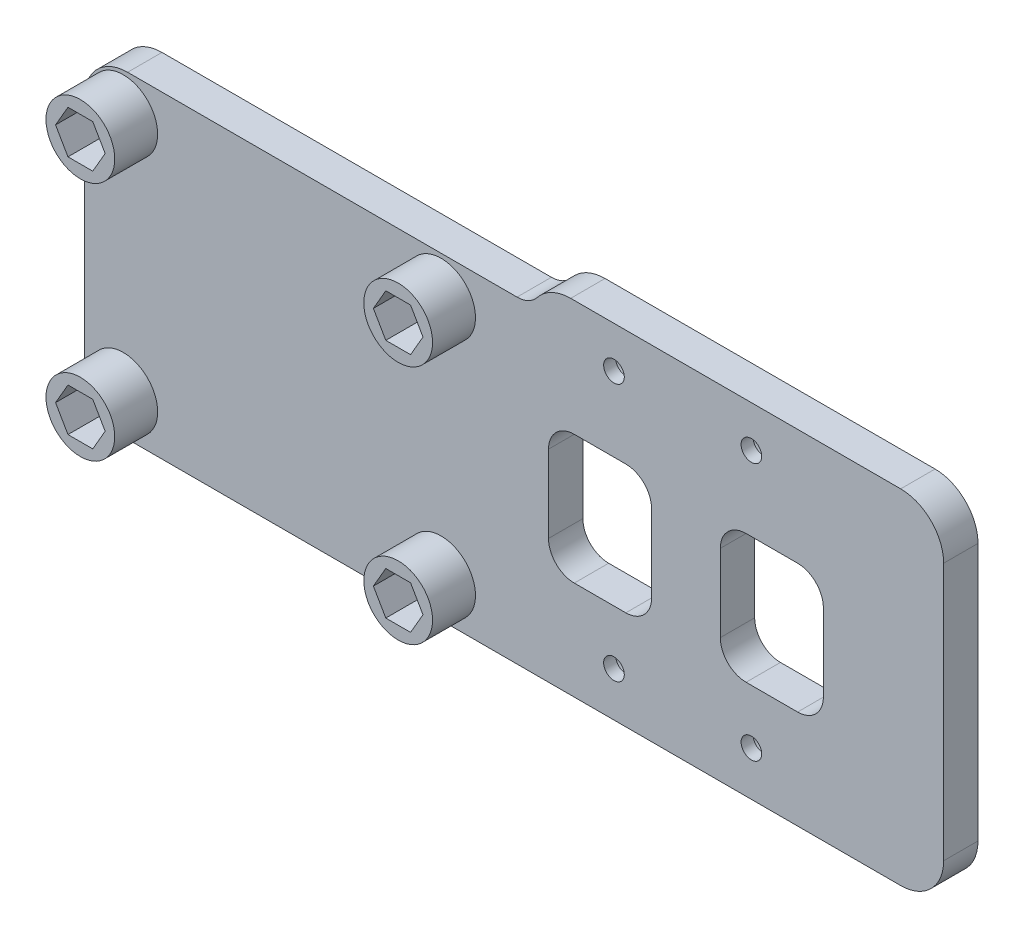
SolidWorks part; units mm, degrees
ref_plane "Front Plane" through (0, 0, 0) normal (0, 0, 1) x (1, 0, 0)
ref_plane "Top Plane" through (0, 0, 0) normal (0, 1, 0) x (1, 0, 0)
ref_plane "Right Plane" through (0, 0, 0) normal (1, 0, 0) x (0, 0, -1)
ref_plane "Plane1" through (0, 0, 34.8116) normal (0, 0, -1) x (-1, 0, 0)
sketch "Sketch1" plane through (0, 0, 34.8116) normal (0, 0, -1) x (-1, 0, 0)
  line L0 (-23.5355, 118.8347) -> (-23.5355, 78.8347)
  line L1 (-23.5355, 78.8347) -> (26.4645, 78.8347)
  line L2 (26.4645, 78.8347) -> (26.4645, 118.8347)
  line L3 (26.4645, 118.8347) -> (-23.5355, 118.8347)
extrude "Boss-Extrude1" add sketch "Sketch1" against normal blind 4
sketch "Sketch2" plane through (0, 0, 38.8116) normal (0, 0, 1) x (1, 0, 0)
  line L0 (23.5355, 90.3347) -> (23.5355, 105.3347)
  line L1 (23.5355, 105.3347) -> (15.5355, 105.3347)
  line L2 (15.5355, 105.3347) -> (15.5355, 90.3347)
  line L3 (15.5355, 90.3347) -> (23.5355, 90.3347)
  line L4 (23.5355, 118.8347) -> (23.5355, 78.8347) construction
  line L6 (15.5355, 105.3347) -> (23.5355, 90.3347) construction
  line L7 (15.5355, 90.3347) -> (23.5355, 105.3347) construction
  line L8 (23.5355, 78.8347) -> (-26.4645, 78.8347) construction
  point P6 (19.5355, 97.8347)
  dimension "D1" = 8
  dimension "D2" = 15
  dimension "D3" = 19
extrude "Cut-Extrude1" cut sketch "Sketch2" against normal through all
sketch "Sketch3" plane through (0, 0, 38.8116) normal (0, 0, 1) x (1, 0, 0)
  line L0 (7.5355, 105.3347) -> (-4.4645, 105.3347)
  line L1 (-4.4645, 105.3347) -> (-4.4645, 90.3347)
  line L2 (-4.4645, 90.3347) -> (7.5355, 90.3347)
  line L3 (7.5355, 90.3347) -> (7.5355, 105.3347)
  line L4 (23.5355, 105.3347) -> (15.5355, 105.3347) construction
  line L5 (15.5355, 90.3347) -> (23.5355, 90.3347) construction
  line L6 (15.5355, 105.3347) -> (15.5355, 90.3347) construction
  dimension "D1" = 8
  dimension "D2" = 12
extrude "Cut-Extrude2" cut sketch "Sketch3" against normal through all
hole_wizard "CBORE for M2 Pan Head Machine Screw1" positions "Sketch5" profile "Sketch4" counterbore size "M2" standard "ANSI Metric" end condition up to next
sketch "Sketch5" plane through (0, 0, 34.8116) normal (0, 0, -1) x (-1, 0, 0)
  point P0 (-3.1566, 84.0163)
  point P1 (-19.1566, 84.0163)
  point P2 (-19.1566, 114.0163)
  point P3 (-3.1566, 114.0163)
sketch "Sketch4" plane through (3.1566, 84.0163, 34.8116) normal (1, 0, 0) x (0, 1, 0)
  line L0 (0, 0) -> (0, 4)
  line L1 (0, 4) -> (1.2, 4)
  line L3 (1.2, 4) -> (1.2, 2.6)
  line L4 (1.2, 2.6) -> (2.5, 2.6)
  line L5 (2.5, 2.6) -> (2.5, 0)
  line L7 (2.5, 0) -> (0, 0)
  line L11 (0, -6.35) -> (0, 107.95) construction
  dimension "Thru Hole Dia." = 2.4
  dimension "Thru Hole Depth" = 4
  dimension "C'Bore Dia." = 5
  dimension "C'Bore Depth" = 2.6
sketch "Sketch6" plane through (0, 0, 38.8116) normal (0, 0, 1) x (1, 0, 0)
  line L0 (-26.4645, 78.8347) -> (-26.4645, 118.8347) construction
  line L1 (-11.4645, 78.8347) -> (-58.4645, 78.8347)
  line L2 (-11.4645, 78.8347) -> (-11.4645, 115.8347)
  line L3 (-11.4645, 115.8347) -> (-58.4645, 115.8347)
  line L4 (-58.4645, 78.8347) -> (-58.4645, 115.8347)
  line L7 (23.5355, 78.8347) -> (-26.4645, 78.8347) construction
  dimension "D1" = 47
  dimension "D2" = 37
  dimension "D3" = 15
extrude "Boss-Extrude2" add sketch "Sketch6" against normal up to surface (4 mm away) up to face at (0.6566, 84.0163, 34.8116)
sketch "Sketch7" plane through (0, 0, 38.8116) normal (0, 0, 1) x (1, 0, 0)
  line L0 (-53.9645, 111.3347) -> (-53.9645, 83.3347) construction
  line L1 (-58.4645, 97.3347) -> (-53.9645, 97.3347) construction
  line L2 (-58.4645, 115.8347) -> (-58.4645, 78.8347) construction
  line L4 (-11.4645, 78.8347) -> (-11.4645, 115.8347) construction
  circle A0 centre (-53.9645, 111.3347) radius 4
  circle A1 centre (-16.9645, 111.3347) radius 4
  circle A2 centre (-53.9645, 83.3347) radius 4
  circle A3 centre (-16.9645, 83.3347) radius 4
  dimension "D3" = 8
  dimension "D1" = 37
  dimension "D2" = 28
  dimension "D4" = 5.5
extrude "Boss-Extrude3" add sketch "Sketch7" along normal blind 5
hole_wizard "Ø2.7 (2.7) Diameter Hole1" positions "Sketch8" profile "Sketch9" hole size "Ø2.7" standard "ANSI Metric"
sketch "Sketch8" plane through (0, 0, 43.8116) normal (0, 0, 1) x (1, 0, 0)
  point P0 (-53.9645, 111.3347)
  point P3 (-16.9645, 111.3347)
  point P6 (-16.9645, 83.3347)
  point P9 (-53.9645, 83.3347)
sketch "Sketch9" plane through (-53.9645, 111.3347, 43.8116) normal (1, 0, 0) x (0, -1, 0)
  line L0 (0, 0) -> (0, 4.8112)
  line L1 (0, 4.8112) -> (1.35, 4)
  line L2 (1.35, 4) -> (1.35, 0)
  line L5 (1.35, 0) -> (0, 0)
  line L10 (0, 4.8112) -> (-1.35, 4) construction
  line L11 (0, -6.35) -> (0, 107.95) construction
  dimension "Hole Dia." = 2.7
  dimension "Hole Depth" = 4
  dimension "Drill Angle" = 118
sketch "Sketch10" plane through (0, 0, 43.8116) normal (0, 0, 1) x (1, 0, 0)
  line L0 (-26.4645, 115.8347) -> (-58.4645, 115.8347) construction
  line L1 (-52.5211, 113.8347) -> (-55.4078, 113.8347)
  line L2 (-55.4078, 113.8347) -> (-56.8512, 111.3347)
  line L3 (-56.8512, 111.3347) -> (-55.4078, 108.8347)
  line L4 (-55.4078, 108.8347) -> (-52.5211, 108.8347)
  line L5 (-52.5211, 108.8347) -> (-51.0777, 111.3347)
  line L6 (-51.0777, 111.3347) -> (-52.5211, 113.8347)
  line L8 (-52.5211, 85.8347) -> (-55.4078, 85.8347)
  line L9 (-55.4078, 85.8347) -> (-56.8512, 83.3347)
  line L10 (-56.8512, 83.3347) -> (-55.4078, 80.8347)
  line L11 (-55.4078, 80.8347) -> (-52.5211, 80.8347)
  line L12 (-52.5211, 80.8347) -> (-51.0777, 83.3347)
  line L13 (-51.0777, 83.3347) -> (-52.5211, 85.8347)
  line L14 (-15.5211, 113.8347) -> (-18.4078, 113.8347)
  line L15 (-18.4078, 113.8347) -> (-19.8512, 111.3347)
  line L16 (-19.8512, 111.3347) -> (-18.4078, 108.8347)
  line L17 (-18.4078, 108.8347) -> (-15.5211, 108.8347)
  line L18 (-15.5211, 108.8347) -> (-14.0777, 111.3347)
  line L19 (-14.0777, 111.3347) -> (-15.5211, 113.8347)
  line L20 (-15.5211, 85.8347) -> (-18.4078, 85.8347)
  line L21 (-18.4078, 85.8347) -> (-19.8512, 83.3347)
  line L22 (-19.8512, 83.3347) -> (-18.4078, 80.8347)
  line L23 (-18.4078, 80.8347) -> (-15.5211, 80.8347)
  line L24 (-15.5211, 80.8347) -> (-14.0777, 83.3347)
  line L25 (-14.0777, 83.3347) -> (-15.5211, 85.8347)
  circle A0 centre (-53.9645, 111.3347) radius 2.5 construction
  circle A1 centre (-53.9645, 83.3347) radius 2.5 construction
  circle A2 centre (-16.9645, 111.3347) radius 2.5 construction
  circle A3 centre (-16.9645, 83.3347) radius 2.5 construction
  dimension "D1" = 5
extrude "Cut-Extrude3" cut sketch "Sketch10" against normal blind 6.5
sketch "Sketch11" plane through (0, 0, 38.8116) normal (0, 0, 1) x (1, 0, 0)
  line L0 (23.5355, 118.8347) -> (41.5355, 118.8347)
  line L1 (41.5355, 118.8347) -> (41.5355, 78.8347)
  line L2 (41.5355, 78.8347) -> (23.5355, 78.8347)
  line L3 (23.5355, 78.8347) -> (23.5355, 90.3347)
  line L4 (23.5355, 90.3347) -> (23.5355, 78.8347) construction
  line L5 (23.5355, 90.3347) -> (27.5355, 90.3347)
  line L6 (27.5355, 90.3347) -> (27.5355, 105.3347)
  line L7 (27.5355, 105.3347) -> (23.5355, 105.3347)
  line L8 (23.5355, 105.3347) -> (23.5355, 118.8347)
  line L9 (23.5355, 78.8347) -> (-58.4645, 78.8347) construction
  line L10 (23.5355, 105.3347) -> (15.5355, 105.3347) construction
  line L11 (15.5355, 90.3347) -> (23.5355, 90.3347) construction
  line L12 (15.5355, 105.3347) -> (15.5355, 90.3347) construction
  line L13 (-58.4645, 115.8347) -> (-58.4645, 78.8347) construction
  dimension "D1" = 12
  dimension "D2" = 100
extrude "Boss-Extrude4" add sketch "Sketch11" against normal up to surface (4 mm away) up to face at (-4.4645, 101.8347, 34.8116)
sketch "Sketch12" plane through (0, 0, 38.8116) normal (0, 0, 1) x (1, 0, 0)
  line L0 (-26.4645, 115.8347) -> (-6.4645, 115.8347)
  line L1 (-6.4645, 115.8347) -> (-6.4645, 118.8347)
  line L2 (-26.4645, 118.8347) -> (41.5355, 118.8347) construction
  line L3 (-6.4645, 118.8347) -> (-26.4645, 118.8347)
  line L4 (-26.4645, 118.8347) -> (-26.4645, 115.8347)
  dimension "D1" = 20
extrude "Cut-Extrude4" cut sketch "Sketch12" against normal blind 10
sketch "Sketch13" plane through (0, 0, 34.8116) normal (0, 0, 1) x (1, 0, 0)
  line L3 (41.5355, 78.8347) -> (41.5355, 118.8347) construction
  line L4 (36.5355, 110.8347) -> (-53.4645, 110.8347) construction
  line L5 (36.5355, 110.8347) -> (36.5355, 83.8347) construction
  line L6 (36.5355, 83.8347) -> (-53.4645, 83.8347) construction
  line L7 (-53.4645, 110.8347) -> (-53.4645, 83.8347) construction
  line L8 (41.5355, 78.8347) -> (-58.4645, 78.8347) construction
  line L9 (-58.4645, 115.8347) -> (-58.4645, 78.8347) construction
  line L10 (-58.4645, 97.3347) -> (-53.4645, 97.3347) construction
  line L11 (-8.4645, 78.8347) -> (-8.4645, 83.8347) construction
  line L12 (36.5355, 110.8347) -> (-53.4645, 83.8347) construction
  line L13 (36.5355, 83.8347) -> (-53.4645, 110.8347) construction
  circle A4 centre (36.5355, 110.8347) radius 2.6
  circle A5 centre (36.5355, 83.8347) radius 2.6
  circle A6 centre (-53.4645, 110.8347) radius 2.6
  circle A7 centre (-53.4645, 83.8347) radius 2.6
  circle A8 centre (-8.4645, 97.3347) radius 2.6
  dimension "D1" = 5
  dimension "D2" = 5
  dimension "D3" = 5.2
extrude "Cut-Extrude5" cut sketch "Sketch13" along normal blind 2.2
sketch "Sketch14" plane through (0, 0, 34.8116) normal (0, 0, -1) x (-1, 0, 0)
  line L0 (-41.5355, 78.8347) -> (-41.5355, 118.8347) construction
  line L1 (-41.5355, 105.8347) -> (-31.5355, 105.8347)
  line L2 (-41.5355, 105.8347) -> (-41.5355, 115.8347) construction
  line L3 (-41.5355, 115.8347) -> (-31.5355, 115.8347)
  line L4 (-31.5355, 105.8347) -> (-31.5355, 115.8347)
  line L5 (-41.5355, 105.8347) -> (-31.5355, 115.8347) construction
  line L6 (-41.5355, 115.8347) -> (-31.5355, 105.8347) construction
  line L7 (-41.5355, 115.8347) -> (-41.5355, 118.8347)
  line L8 (6.4645, 118.8347) -> (-41.5355, 118.8347) construction
  line L9 (-41.5355, 118.8347) -> (6.4645, 118.8347)
  line L10 (6.4645, 118.8347) -> (6.4645, 115.8347)
  line L11 (6.4645, 115.8347) -> (58.4645, 115.8347)
  line L12 (58.4645, 115.8347) -> (58.4645, 78.8347)
  line L13 (58.4645, 78.8347) -> (-41.5355, 78.8347)
  line L14 (-41.5355, 78.8347) -> (-41.5355, 105.8347)
  circle A0 centre (-36.5355, 110.8347) radius 2.6 construction
  point P0 (-36.5355, 110.8347)
extrude "Cut-Extrude6" [suppressed] cut sketch "Sketch14" against normal up to next
fillet "Fillet1" radius 5 5 edges at (-58.4645, 115.8347, 36.8116) (-58.4645, 78.8347, 36.8116) (41.5355, 78.8347, 36.8116) (41.5355, 118.8347, 36.8116) (-6.4645, 118.8347, 36.8116)
fillet "Fillet2" radius 3 8 edges at (7.5355, 90.3347, 36.8116) (-4.4645, 90.3347, 36.8116) (15.5355, 90.3347, 36.8116) (27.5355, 90.3347, 36.8116) (15.5355, 105.3347, 36.8116) (7.5355, 105.3347, 36.8116) (-4.4645, 105.3347, 36.8116) (27.5355, 105.3347, 36.8116)
fillet "Fillet3" radius 3 1 edges at (-6.4645, 115.8347, 36.8116)
